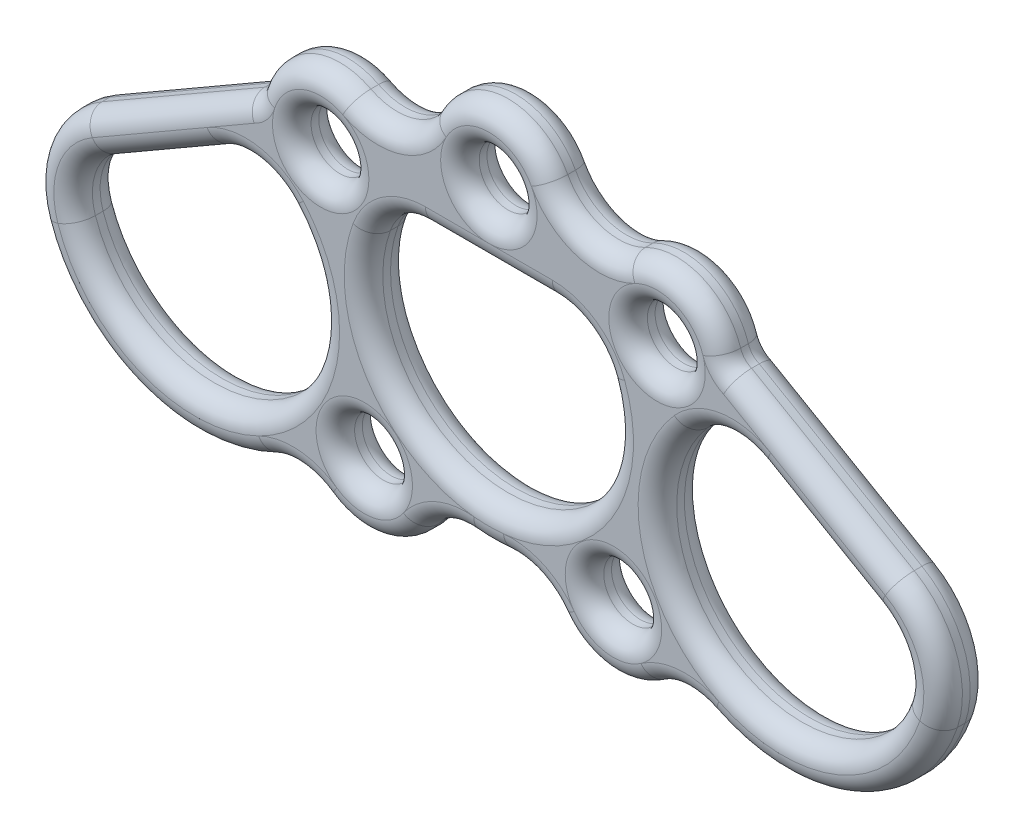
SolidWorks part; units mm, degrees
material "7075-T6 (SN)"
ref_plane "Front Plane" through (0, 0, 0) normal (0, 0, 1) x (1, 0, 0)
ref_plane "Top Plane" through (0, 0, 0) normal (0, 1, 0) x (1, 0, 0)
ref_plane "Right Plane" through (0, 0, 0) normal (1, 0, 0) x (0, 0, -1)
sketch "Sketch1" plane through (0, 0, 0) normal (0, 0, 1) x (1, 0, 0)
  line L0 (-24.8042, 21) -> (24.8042, 21)
  line L1 (0, 0) -> (0, 38.5) construction
  line L2 (-62.2762, 15.9619) -> (-108.5938, -10.7796)
  line L3 (62.2762, 15.9619) -> (108.5938, -10.7796)
  line L4 (-63.1077, 27.0288) -> (-117.7623, -4.526)
  line L5 (-29.0732, 31) -> (29.0732, 31)
  line L6 (63.1077, 27.0288) -> (117.7623, -4.526)
  arc A0 (-24.8042, 21) -> (24.8042, 21) centre (0, 0) ccw
  circle A1 centre (0, 38.5) radius 7.5
  circle A2 centre (-43.6, 24.8392) radius 7.5
  circle A3 centre (-32.3, -38.328) radius 7.5
  arc A4 (-108.5938, -10.7796) -> (-62.2762, 15.9619) centre (-76.2, -13.4044) ccw
  circle A5 centre (32.3, -38.328) radius 7.5
  arc A6 (108.5938, -10.7796) -> (62.2762, 15.9619) centre (76.2, -13.4044) cw
  circle A7 centre (43.6, 24.8392) radius 7.5
  arc A8 (-117.7623, -4.526) -> (-63.1077, 27.0288) centre (-76.2, -13.4044) ccw
  circle A9 centre (-43.6, 24.8392) radius 17.5
  circle A10 centre (0, 38.5) radius 17.5
  circle A11 centre (-32.3, -38.328) radius 17.5
  arc A12 (-29.0732, 31) -> (29.0732, 31) centre (0, 0) ccw
  arc A13 (117.7623, -4.526) -> (63.1077, 27.0288) centre (76.2, -13.4044) cw
  circle A14 centre (43.6, 24.8392) radius 17.5
  circle A15 centre (32.3, -38.328) radius 17.5
  arc A16 (-35.5831, 40.3949) -> (-15.46, 46.6999) centre (-28.7114, 53.7284) ccw
  arc A17 (35.5831, 40.3949) -> (15.46, 46.6999) centre (28.7114, 53.7284) cw
  arc A18 (-57.4626, -51.5509) -> (-42.2882, -52.6976) centre (-50.8495, -65.0144) cw
  arc A19 (-18.0536, -48.4911) -> (-4.3183, -42.28) centre (-5.8424, -57.2024) cw
  arc A20 (57.4626, -51.5509) -> (42.2882, -52.6976) centre (50.8495, -65.0144) ccw
  arc A21 (18.0536, -48.4911) -> (4.3183, -42.28) centre (5.8424, -57.2024) ccw
  point P48 (0, 0)
  point P52 (-10.1196, -48.2476)
  dimension "D1" = 32.5
  dimension "D2" = 15
  dimension "D15" = 15
  dimension "D16" = 15
  dimension "D17" = 15
  dimension "D3" = 38.5
  dimension "D4" = 87.2
  dimension "D5" = 64.6
  dimension "D6" = 152.4
  dimension "D7" = 21
  dimension "D8" = 50.97
  dimension "D9" = 64.17
  dimension "D10" = 45.69
  dimension "D11" = 77.37
  dimension "D12" = 60
  dimension "D13" = 10
  dimension "D14" = 10
extrude "Boss-Extrude1" add sketch "Sketch1" along normal blind 12 contours A12 A9 A8 L4 A11 A4 L2 | A12 A8 A9 | A12 L5 A9 A8 A2 | L5 A12 A8 A9 | A8 A12 A9 | A9 A12 A11 A8 | A12 A15 A13 A14 L5 A10 L0 A0 A9 A8 A11 | A8 A12 A11 | A11 A12 A8 | A12 A11 A8 | A12 A8 A11 A3 | L5 A10 A1 | A10 L1 L5 | L1 A10 L5 | A14 L5 A12 A13 A7 | A14 A13 A12 L5 | A14 A13 A12 | A14 A12 A13 | A13 A15 A12 A14 | A12 A15 A13 L6 A14 L3 A6 | A15 A13 A12 A5 | A15 A12 A13 | A15 A13 A12 | A15 A12 A13 | A16 A9 L5 A10 | A14 A17 A10 L5 | A8 A18 A11 | A11 A19 A12 | A21 A15 A12 | A20 A13 A15 region at (9.9301, 22.7991, 0) region at (-6.2455, 26.8823, 0) region at (6.2455, 26.8823, 0) region at (-7.9057, 31.4301, 0) region at (-22.8716, 36.0154, 0) region at (22.8716, 36.0154, 0) region at (-32.8853, 18.9496, 0) region at (-28.1467, 31.4636, 0) region at (30.8747, 36.1665, 0) region at (32.8853, 18.9496, 0) region at (38.0952, -6.7298, 0) region at (40.7971, 8.6353, 0) region at (-51.7531, 15.6877, 0) region at (-40.7971, 8.6353, 0) region at (-38.0952, -6.7298, 0) region at (-55.9514, 12.2778, 0) region at (51.7531, 15.6877, 0) region at (62.4564, 25.5777, 0) region at (35.3826, -22.1261, 0) region at (24.2646, -29.1706, 0) region at (-24.2646, -29.1706, 0) region at (-35.3826, -22.1261, 0) region at (39.6533, -35.9878, 0) region at (43.186, -32.4377, 0) region at (12.8865, -42.6503, 0) region at (-43.186, -32.4377, 0) region at (-26.2033, -33.5196, 0) region at (49.1993, -48.8935, 0) region at (-49.1993, -48.8935, 0) region at (-12.8865, -42.6503, 0)
fillet "Fillet1" radius 15 6 edges at (108.5938, -10.7796, 6) (62.2762, 15.9619, 6) (-24.8042, 21, 6) (-108.5938, -10.7796, 6) (24.8042, 21, 6) (-62.2762, 15.9619, 6)
fillet "Fillet2" radius 5 2 edges at (-61.039, 26.2995, 6) (61.039, 26.2995, 6)
fillet "Fillet3" radius 25 2 edges at (117.7623, -4.526, 6) (-117.7623, -4.526, 6)
fillet "Fillet4" radius 5 74 edges at (39.8, -38.328, 0) (106.8195, -13.6689, 0) (59.95, -41.5502, 0) (60.6612, 12.9806, 0) (85.435, 2.5911, 0) (51.1, 24.8392, 0) (-36.1, 24.8392, 0) (-24.8, -38.328, 0) (-60.6612, 12.9806, 0) (-59.95, -41.5502, 0) (-106.8195, -13.6689, 0) (-85.435, 2.5911, 0) (25.0375, 18.2911, 0) (0, -32.5, 0) (-25.0375, 18.2911, 0) (0, 21, 0) (7.5, 38.5, 0) (61.3547, 28.2671, 0) (50.3182, 40.9983, 0) (24.2266, 39.4145, 0) (0, 56, 0) (-24.2266, 39.4145, 0) (-50.3182, 40.9983, 0) (-61.3547, 28.2671, 0) (-84.1986, 14.852, 0) (-116.1728, -10.1311, 0) (-92.5588, -52.6298, 0) (-29.3072, -55.5702, 0) (0, -42.5, 0) (29.3072, -55.5702, 0) (92.5588, -52.6298, 0) (116.1728, -10.1311, 0) (84.1986, 14.852, 0) (39.8, -38.328, 12) (106.8195, -13.6689, 12) (85.435, 2.5911, 12) (60.6612, 12.9806, 12) (59.95, -41.5502, 12) (51.1, 24.8392, 12) (-36.1, 24.8392, 12) (-24.8, -38.328, 12) (-60.6612, 12.9806, 12) (-85.435, 2.5911, 12) (-106.8195, -13.6689, 12) (-59.95, -41.5502, 12) (25.0375, 18.2911, 12) (0, 21, 12) (-25.0375, 18.2911, 12) (0, -32.5, 12) (7.5, 38.5, 12) (29.3072, -55.5702, 12) (0, -42.5, 12) (-29.3072, -55.5702, 12) (-92.5588, -52.6298, 12) (-116.1728, -10.1311, 12) (-84.1986, 14.852, 12) (-61.3547, 28.2671, 12) (-50.3182, 40.9983, 12) (-24.2266, 39.4145, 12) (0, 56, 12) (24.2266, 39.4145, 12) (50.3182, 40.9983, 12) (61.3547, 28.2671, 12) (84.1986, 14.852, 12) (116.1728, -10.1311, 12) (92.5588, -52.6298, 12) (-49.7192, -50.0571, 0) (-12.0228, -43.5349, 0) (12.0228, -43.5349, 0) (49.7192, -50.0571, 0) (49.7192, -50.0571, 12) (12.0228, -43.5349, 12) (-12.0228, -43.5349, 12) (-49.7192, -50.0571, 12)
